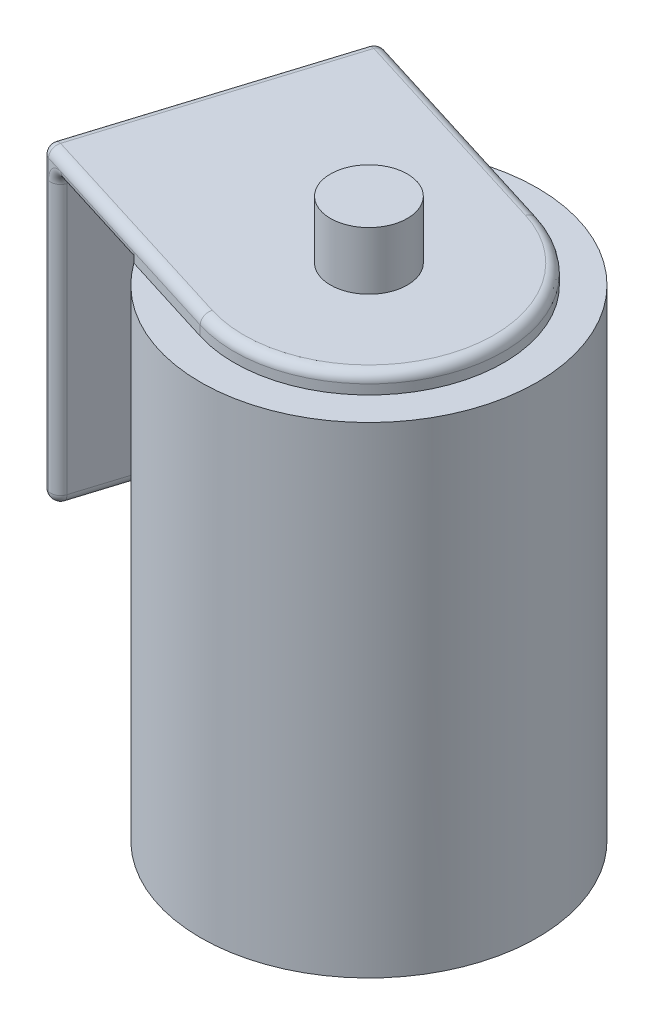
SolidWorks part; units mm, degrees
ref_plane "Plan de face" through (0, 0, 0) normal (0, 0, 1) x (1, 0, 0)
ref_plane "Plan de dessus" through (0, 0, 0) normal (0, 1, 0) x (1, 0, 0)
ref_plane "Plan de droite" through (0, 0, 0) normal (1, 0, 0) x (0, 0, -1)
sketch "Esquisse1" plane through (0, 0, 0) normal (0, 1, 0) x (1, 0, 0)
  circle A0 centre (0, 0) radius 17.5
  dimension "D1" = 35
extrude "Boss.-Extru.1" add sketch "Esquisse1" along normal blind 50
sketch "Esquisse2" plane through (0, 50, 0) normal (0, 1, 0) x (1, 0, 0)
  circle A0 centre (0, 0) radius 4
  dimension "D1" = 8
extrude "Boss.-Extru.2" add sketch "Esquisse2" along normal blind 8 contours A0
sketch "Esquisse3" plane through (0, 50, 0) normal (0, 1, 0) x (1, 0, 0)
  line L0 (4.1677, 13.3653) -> (-19.6988, 20.8076)
  line L1 (-4.1677, -13.3653) -> (-28.0343, -5.9229)
  line L2 (-19.6988, 20.8076) -> (-28.0343, -5.9229)
  arc A0 (-4.1677, -13.3653) -> (4.1677, 13.3653) centre (0, 0) ccw
  dimension "D2" = 14
  dimension "D1" = 25
extrude "Boss.-Extru.3" add sketch "Esquisse3" along normal blind 2
sketch "Esquisse4" plane through (0, 50, 0) normal (0, -1, 0) x (1, 0, 0)
  line L0 (-28.0343, 5.9229) -> (-19.6988, -20.8076)
  line L1 (-28.0343, 5.9229) -> (-26.1249, 6.5183)
  line L2 (-19.6988, -20.8076) -> (-17.7895, -20.2122)
  line L3 (-26.1249, 6.5183) -> (-17.7895, -20.2122)
  dimension "D1" = 2
extrude "Boss.-Extru.4" add sketch "Esquisse4" along normal blind 30
fillet "Congé1" radius 1 1 edges at (-23.8665, 52, -7.4424)
fillet "Congé2" radius 1 14 edges at (-27.7546, 51.7071, 6.0101) (-19.4192, 51.7071, -20.7204) (-11.8229, 50, -18.3516) (-19.6988, 35.5, -20.8076) (-17.7895, 35, -20.2122) (-21.9572, 50, -6.847) (-20.1583, 50, 8.3789) (-23.8665, 20, -7.4424) (-21.9572, 20, -6.847) (-28.0343, 35.5, 5.9229) (-26.1249, 35, 6.5183) (13.3653, 52, 4.1677) (-7.2882, 52, -16.9376) (-15.6237, 52, 9.7929)
